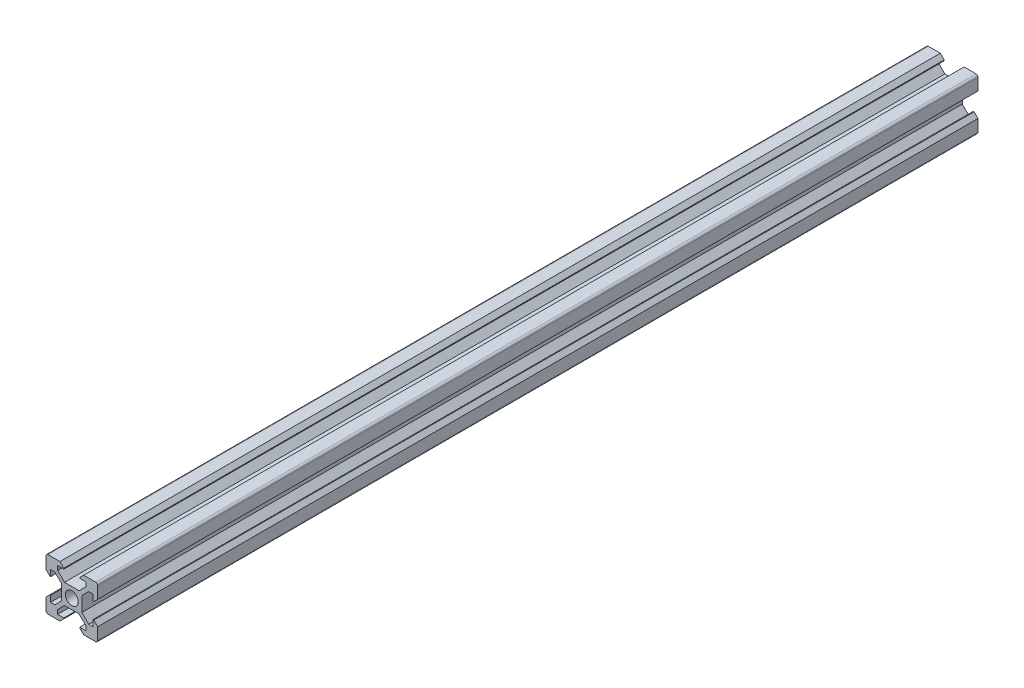
SolidWorks part; units mm, degrees
other "Markup1"
sketch "Sketch1" plane through (10, 10, 480) normal (0.5774, 0.5773, 0.5774) x (0.7071, 0, -0.7071)
ref_plane "Alzado" through (0, 0, 0) normal (0, 0, 1) x (1, 0, 0)
ref_plane "Planta" through (0, 0, 0) normal (0, 1, 0) x (1, 0, 0)
ref_plane "Vista lateral" through (0, 0, 0) normal (1, 0, 0) x (0, 0, -1)
sketch "Croquis1" plane through (0, 0, 0) normal (0, 0, 1) x (1, 0, 0)
  line L0 (-4.6, 10) -> (-3.1, 8.5)
  line L3 (-4.6, 10) -> (-9.25, 10)
  line L5 (-3.1, 8.5) -> (-3.1, 8.2)
  line L6 (-3.1, 8.2) -> (-5.5, 8.2)
  line L7 (-5.5, 8.2) -> (-5.5, 6.5607)
  line L8 (-5.5, 6.5607) -> (-2.84, 3.9007)
  line L9 (-2.84, 3.9007) -> (0, 3.9007)
  line L10 (0, 0) -> (-15.3499, 15.3499) construction
  line L11 (-3.9007, 2.84) -> (-3.9007, 0)
  line L12 (-6.5607, 5.5) -> (-3.9007, 2.84)
  line L13 (-8.2, 5.5) -> (-6.5607, 5.5)
  line L14 (-8.2, 3.1) -> (-8.2, 5.5)
  line L15 (-8.5, 3.1) -> (-8.2, 3.1)
  line L16 (-10, 4.6) -> (-10, 9.25)
  line L17 (-10, 4.6) -> (-8.5, 3.1)
  line L18 (10, 4.6) -> (8.5, 3.1)
  line L19 (10, 4.6) -> (10, 9.25)
  line L20 (8.5, 3.1) -> (8.2, 3.1)
  line L21 (8.2, 3.1) -> (8.2, 5.5)
  line L22 (8.2, 5.5) -> (6.5607, 5.5)
  line L23 (6.5607, 5.5) -> (3.9007, 2.84)
  line L24 (3.9007, 2.84) -> (3.9007, 0)
  line L25 (5.5, 6.5607) -> (2.84, 3.9007)
  line L26 (5.5, 8.2) -> (5.5, 6.5607)
  line L27 (3.1, 8.2) -> (5.5, 8.2)
  line L28 (3.1, 8.5) -> (3.1, 8.2)
  line L29 (4.6, 10) -> (9.25, 10)
  line L30 (4.6, 10) -> (3.1, 8.5)
  line L31 (2.84, 3.9007) -> (0, 3.9007)
  line L32 (4.6, -10) -> (3.1, -8.5)
  line L33 (4.6, -10) -> (9.25, -10)
  line L34 (3.1, -8.5) -> (3.1, -8.2)
  line L35 (3.1, -8.2) -> (5.5, -8.2)
  line L36 (5.5, -8.2) -> (5.5, -6.5607)
  line L37 (5.5, -6.5607) -> (2.84, -3.9007)
  line L38 (2.84, -3.9007) -> (0, -3.9007)
  line L39 (6.5607, -5.5) -> (3.9007, -2.84)
  line L40 (8.2, -5.5) -> (6.5607, -5.5)
  line L41 (8.2, -3.1) -> (8.2, -5.5)
  line L42 (8.5, -3.1) -> (8.2, -3.1)
  line L43 (10, -4.6) -> (10, -9.25)
  line L44 (10, -4.6) -> (8.5, -3.1)
  line L45 (3.9007, -2.84) -> (3.9007, 0)
  line L46 (-10, -4.6) -> (-8.5, -3.1)
  line L47 (-10, -4.6) -> (-10, -9.25)
  line L48 (-8.5, -3.1) -> (-8.2, -3.1)
  line L49 (-8.2, -3.1) -> (-8.2, -5.5)
  line L50 (-8.2, -5.5) -> (-6.5607, -5.5)
  line L51 (-6.5607, -5.5) -> (-3.9007, -2.84)
  line L52 (-3.9007, -2.84) -> (-3.9007, 0)
  line L53 (-5.5, -6.5607) -> (-2.84, -3.9007)
  line L54 (-5.5, -8.2) -> (-5.5, -6.5607)
  line L55 (-3.1, -8.2) -> (-5.5, -8.2)
  line L56 (-3.1, -8.5) -> (-3.1, -8.2)
  line L57 (-4.6, -10) -> (-9.25, -10)
  line L58 (-4.6, -10) -> (-3.1, -8.5)
  line L59 (-2.84, -3.9007) -> (0, -3.9007)
  circle A0 centre (0, 0) radius 2.5
  arc A1 (-9.25, 10) -> (-10, 9.25) centre (-9.25, 9.25) ccw
  arc A2 (10, 9.25) -> (9.25, 10) centre (9.25, 9.25) ccw
  arc A3 (9.25, -10) -> (10, -9.25) centre (9.25, -9.25) ccw
  arc A4 (-10, -9.25) -> (-9.25, -10) centre (-9.25, -9.25) ccw
  point P18 (-10, 10)
  point P37 (10, 10)
  point P55 (10, -10)
  point P73 (-10, -10)
  point P79 (0, 0)
  dimension "D1" = 5
  dimension "D5" = 0.75
  dimension "D2" = 10
  dimension "D3" = 10
  dimension "D4" = 4.6
  dimension "D6" = 5.5
  dimension "D7" = 135
  dimension "D8" = 0.75
  dimension "D9" = 225
  dimension "D10" = 2.84
  dimension "D11" = 1.8
  dimension "D12" = 3.1
  dimension "D13" = 4
extrude "Saliente-Extruir1" add sketch "Croquis1" along normal blind 341.39
